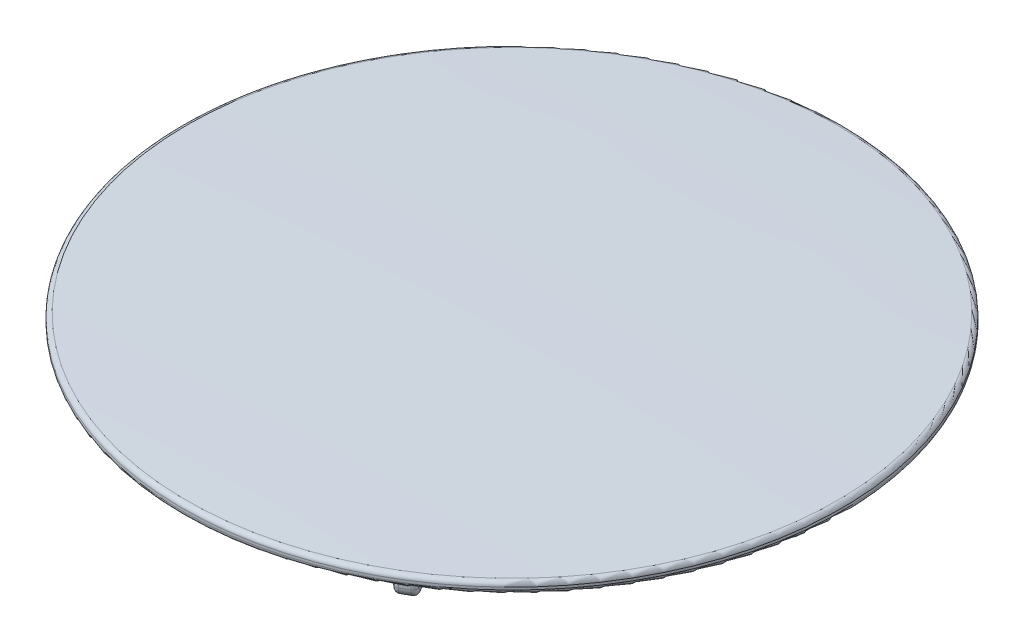
SolidWorks part; units mm, degrees
material "Chrome Stainless Steel"
ref_plane "Front Plane" through (0, 0, 0) normal (0, 0, 1) x (1, 0, 0)
ref_plane "Top Plane" through (0, 0, 0) normal (0, 1, 0) x (1, 0, 0)
ref_plane "Right Plane" through (0, 0, 0) normal (1, 0, 0) x (0, 0, -1)
ref_plane "SinkDrainTopPlane" through (0, -228.6, 0) normal (0, 1, 0) x (1, 0, 0)
sketch "DrainPosSketch" plane through (0, -228.6, 0) normal (0, 1, 0) x (1, 0, 0)
  line L0 (419.1, 444.5) -> (419.1, 38.1) construction
  line L1 (0, 0) -> (838.2, 0) construction
  line L2 (0, 0) -> (0, 558.8) construction
  line L3 (0, 558.8) -> (838.2, 558.8) construction
  line L4 (838.2, 0) -> (838.2, 558.8) construction
  line L5 (25.4, 38.1) -> (812.8, 38.1) construction
  line L6 (25.4, 38.1) -> (25.4, 444.5) construction
  line L7 (25.4, 444.5) -> (812.8, 444.5) construction
  line L8 (812.8, 38.1) -> (812.8, 444.5) construction
  line L13 (25.4, 241.3) -> (812.8, 241.3) construction
  circle A0 centre (685.8, 317.5) radius 44.45 construction
  circle A5 centre (685.8, 317.5) radius 57.15
  dimension "D7" = 88.9
  dimension "D13" = 114.3
  dimension "D1" = 838.2
  dimension "D2" = 558.8
  dimension "D3" = 406.4
  dimension "D4" = 787.4
  dimension "D5" = 25.4
  dimension "D6" = 114.3
  dimension "D8" = 127
  dimension "D9" = 127
ref_plane "DrainProfilePlanePlane" through (0, 0, -317.5) normal (0, 0, 1) x (1, 0, 0)
sketch "DrainCoverSketch" plane through (0, 0, -317.5) normal (0, 0, 1) x (1, 0, 0)
  line L0 (685.8, -228.6) -> (685.8, -322.2625) construction
  line L1 (742.95, -228.6) -> (628.65, -228.6) construction
  line L2 (628.65, -228.6) -> (742.95, -228.6) construction
  line L3 (25.4, -228.6) -> (812.8, -228.6) construction
  line L4 (730.25, -228.6) -> (730.25, -231.775) construction
  line L5 (730.25, -231.775) -> (685.8, -231.775) construction
  line L6 (742.95, -228.6) -> (742.95, -227.0125) construction
  line L7 (742.95, -227.0125) -> (725.4875, -227.0125) construction
  line L8 (725.4875, -227.0125) -> (725.4875, -231.775) construction
  line L9 (730.25, -231.775) -> (742.95, -231.775) construction
  line L10 (742.95, -231.775) -> (742.95, -237.3313) construction
  line L11 (685.8, -237.3313) -> (746.125, -237.3313) construction
  line L12 (746.125, -237.3313) -> (746.125, -245.2688) construction
  line L13 (746.125, -245.2688) -> (685.8, -245.2688) construction
  line L14 (685.8, -247.2531) -> (744.5375, -247.2531) construction
  line L15 (746.125, -245.6656) -> (746.125, -245.2688) construction
  line L16 (733.425, -247.2531) -> (733.425, -256.7781) construction
  line L17 (733.425, -256.7781) -> (685.8, -256.7781) construction
  line L18 (733.425, -256.7781) -> (717.55, -272.6531) construction
  line L19 (717.55, -272.6531) -> (685.8, -272.6531) construction
  line L20 (685.8, -306.3081) -> (708.025, -306.3081) construction
  line L21 (708.025, -306.3081) -> (717.55, -272.6531) construction
  line L22 (685.8, -322.2625) -> (708.025, -322.2625) construction
  line L23 (708.025, -322.2625) -> (708.025, -306.3081) construction
  line L24 (708.025, -306.3081) -> (709.6125, -307.9353) construction
  line L25 (709.6125, -307.9353) -> (709.6125, -320.6353) construction
  line L26 (709.6125, -320.6353) -> (708.025, -322.2625) construction
  line L27 (709.6125, -314.2853) -> (708.025, -314.2853) construction
  line L28 (725.4875, -231.775) -> (704.85, -304.6942) construction
  line L29 (704.85, -304.6942) -> (704.85, -322.2625) construction
  line L30 (685.8, -220.6625) -> (742.95, -220.6625)
  line L31 (742.95, -220.6625) -> (742.95, -218.6781)
  line L32 (742.95, -218.6781) -> (685.8, -218.6781)
  line L33 (685.8, -217.4875) -> (685.8, -220.6625)
  line L34 (685.8, -217.4875) -> (742.95, -217.4875) construction
  line L35 (736.6, -220.6625) -> (736.6, -227.0125)
  line L36 (736.6, -227.0125) -> (725.4875, -227.0125)
  line L37 (725.4875, -227.0125) -> (725.4875, -233.3625)
  line L38 (725.4875, -233.3625) -> (720.725, -233.3625)
  line L39 (720.725, -233.3625) -> (720.725, -220.6625)
  arc A0 (744.5375, -247.2531) -> (746.125, -245.6656) centre (744.5375, -245.6656) ccw construction
  arc A1 (685.8, -217.4875) -> (742.95, -218.6781) centre (685.8, -1589.6828) cw
  dimension "D10" = 1.5875
  dimension "D1" = 1.5875
  dimension "D2" = 114.3
  dimension "D3" = 3.175
  dimension "D4" = 44.45
  dimension "D5" = 95.25
  dimension "D6" = 39.6875
  dimension "D7" = 5.5562
  dimension "D8" = 7.9375
  dimension "D9" = 1.9844
  dimension "D11" = 60.325
  dimension "D12" = 9.525
  dimension "D13" = 47.625
  dimension "D14" = 31.75
  dimension "D15" = 15.875
  dimension "D16" = 22.225
  dimension "D17" = 33.655
  dimension "D18" = 12.7
  dimension "D19" = 1.5875
  dimension "D20" = 19.05
  dimension "D21" = 6.35
  dimension "D22" = 1.9844
  dimension "D23" = 15.875
  dimension "D24" = 50.8
  dimension "D25" = 12.7
  dimension "D26" = 4.7625
revolve "CoverRevolve" add sketch "DrainCoverSketch" angle 360 about L33 region at (714.375, -219.6703, -317.5) region at (707.2325, -218.2019, -317.5)
fillet "CoverFillet" radius 0.7937 2 edges at (685.8, -218.6781, -260.35) (685.8, -220.6625, -260.35)
extrude "LegBoss-Extrude" add sketch "DrainCoverSketch<5>" along normal mid plane 3.175 separate body contours L39 L38 L37 L36 L35 L30 region at (727.3803, -225.3029, -317.5)
sketch "DrainCoverSketch<5>" plane through (0, 0, -317.5) normal (0, 0, 1) x (1, 0, 0) same geometry as "DrainCoverSketch"
fillet "LegProfileFillet" radius 1.5875 4 edges at (725.4875, -227.0125, -317.5) (736.6, -227.0125, -317.5) (720.725, -233.3625, -317.5) (725.4875, -233.3625, -317.5)
fillet "LegSidesFillet" radius 0.7937 18 edges at (736.6, -223.0438, -319.0875) (736.6, -223.0438, -315.9125) (725.4875, -230.1875, -319.0875) (725.4875, -230.1875, -315.9125) (723.1062, -233.3625, -319.0875) (723.1062, -233.3625, -315.9125) (720.725, -226.2188, -319.0875) (720.725, -226.2188, -315.9125) (736.135, -226.5475, -319.0875) (731.0438, -227.0125, -319.0875) (725.9525, -227.4775, -319.0875) (725.0225, -232.8975, -319.0875) (721.19, -232.8975, -319.0875) (736.135, -226.5475, -315.9125) (731.0438, -227.0125, -315.9125) (725.9525, -227.4775, -315.9125) (725.0225, -232.8975, -315.9125) (721.19, -232.8975, -315.9125)
pattern_circular "LegsCirPattern" count 6 over 360 about axis through (685.8, -220.6625, -317.5) along (0, -1, 0) of bodies 178
combine bodies "CoverCombine" bodies to combine 177 180 179 178 183 182 181
